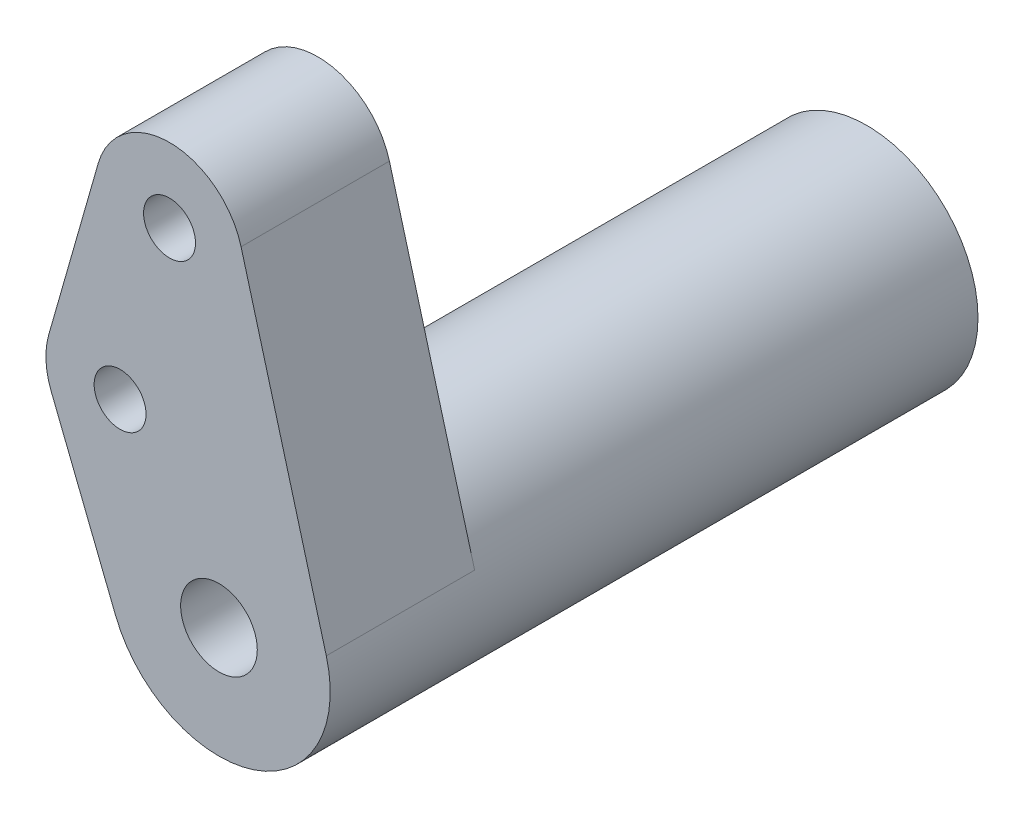
SolidWorks part; units mm, degrees
material "6061-T6 (SS)"
ref_plane "Alzado" through (0, 0, 0) normal (0, 0, 1) x (1, 0, 0)
ref_plane "Planta" through (0, 0, 0) normal (0, 1, 0) x (1, 0, 0)
ref_plane "Vista lateral" through (0, 0, 0) normal (1, 0, 0) x (0, 0, -1)
ref_plane "Plano1" through (0, 0, 14) normal (0, 0, 1) x (1, 0, 0)
sketch "Sk_Columna" plane through (0, 0, 14) normal (0, 0, 1) x (1, 0, 0)
  circle A0 centre (-36, -62) radius 9
  circle A1 centre (-36, -62) radius 3.1
extrude "Columna" add sketch "Sk_Columna" along normal blind 40.4
ref_plane "Plano2" through (0, 0, 54.4) normal (0, 0, 1) x (1, 0, 0)
sketch "Sk_Cuerpo_inferior" plane through (0, 0, 54.4) normal (0, 0, 1) x (1, 0, 0)
  line L0 (-49.5754, -52.2169) -> (-44.3631, -65.3254)
  line L1 (-27.3188, -59.626) -> (-34.2125, -34.4173)
  line L2 (-45.7691, -34.3517) -> (-49.7691, -48.3517)
  arc A0 (-44.3631, -65.3254) -> (-27.3188, -59.626) centre (-36, -62) ccw
  arc A1 (-34.2125, -34.4173) -> (-45.7691, -34.3517) centre (-40, -36) ccw
  arc A2 (-49.7691, -48.3517) -> (-49.5754, -52.2169) centre (-44, -50) ccw
  circle A3 centre (-40, -36) radius 2.1
  circle A4 centre (-44, -50) radius 2.1
  circle A5 centre (-36, -62) radius 3.1
extrude "Cuerpo_inferior" add sketch "Sk_Cuerpo_inferior" along normal blind 12
